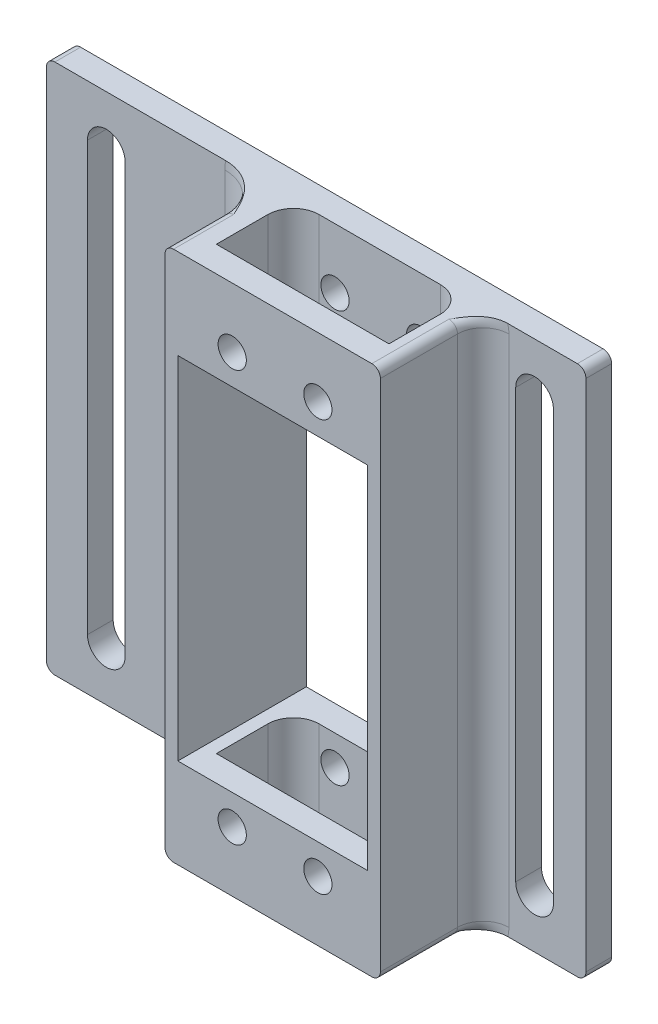
SolidWorks part; units mm, degrees
ref_plane "前视基准面" through (0, 0, 0) normal (0, 0, 1) x (1, 0, 0)
ref_plane "上视基准面" through (0, 0, 0) normal (0, 1, 0) x (1, 0, 0)
ref_plane "右视基准面" through (0, 0, 0) normal (1, 0, 0) x (0, 0, -1)
sketch "草图1" plane through (0, 0, 0) normal (0, 0, 1) x (1, 0, 0)
  line L5 (-28, 6) -> (35, 6)
  line L6 (-28, 6) -> (-28, -56)
  line L7 (-28, -56) -> (35, -56)
  line L8 (35, 6) -> (35, -56)
  line L10 (26.8, 0) -> (26.8, -50)
  line L11 (31.2, 0) -> (31.2, -50)
  line L13 (-23.2, 0) -> (-23.2, -50)
  line L14 (-18.8, 0) -> (-18.8, -50)
  arc A1 (31.2, 0) -> (26.8, 0) centre (29, 0) ccw
  arc A2 (26.8, -50) -> (31.2, -50) centre (29, -50) ccw
  arc A4 (-18.8, 0) -> (-23.2, 0) centre (-21, 0) ccw
  arc A5 (-23.2, -50) -> (-18.8, -50) centre (-21, -50) ccw
  dimension "D3" = 6
  dimension "D4" = 6
  dimension "D5" = 6
  dimension "D6" = 2
  dimension "D7" = 50
  dimension "D8" = 63
  dimension "D2" = 50
  dimension "D10" = 4.4
extrude "凸台-拉伸1" add sketch "草图1" along normal blind 3
sketch "草图2" plane through (0, 0, 3) normal (0, 0, 1) x (1, 0, 0)
  line L0 (35, 6) -> (-28, 6) construction
  line L6 (-2.15, 6) -> (23, 6)
  line L7 (-2.15, 6) -> (-2.15, -56)
  line L8 (-2.15, -56) -> (23, -56)
  line L9 (23, 6) -> (23, -56)
  line L13 (35, -56) -> (35, 6) construction
  circle A0 centre (5.7, -1) radius 1.65
  circle A1 centre (15.7, -1) radius 1.65
  circle A2 centre (15.7, -49) radius 1.65
  circle A3 centre (5.7, -49) radius 1.65
  dimension "D4" = 7
  dimension "D5" = 62
  dimension "D6" = 25.15
  dimension "D7" = 7
  dimension "D3" = 7.85
  dimension "D1" = 10
  dimension "D2" = 48
  dimension "D8" = 62
  dimension "D9" = 12
extrude "凸台-拉伸2" add sketch "草图2" along normal blind 12
sketch "草图4" plane through (0, 0, 15) normal (0, 0, 1) x (1, 0, 0)
  line L1 (-0.65, -4.5) -> (21.5, -4.5)
  line L2 (-0.65, -4.5) -> (-0.65, -45.5)
  line L3 (-0.65, -45.5) -> (21.5, -45.5)
  line L4 (21.5, -4.5) -> (21.5, -45.5)
  line L5 (-2.15, 6) -> (-2.15, -56) construction
  line L6 (23, -56) -> (23, 6) construction
  line L7 (23, 6) -> (-2.15, 6) construction
  line L8 (-2.15, -56) -> (23, -56) construction
  circle A0 centre (5.7, -1) radius 1.65
  circle A1 centre (5.7, -49) radius 1.65
  circle A2 centre (15.7, -49) radius 1.65
  circle A3 centre (15.7, -1) radius 1.65
  dimension "D1" = 1.5
  dimension "D2" = 1.5
  dimension "D3" = 10.5
  dimension "D4" = 10.5
extrude "切除-拉伸4" cut sketch "草图4" against normal blind 45
fillet "圆角1" radius 1 8 edges at (-28, -56, 1.5) (35, -56, 1.5) (35, 6, 1.5) (-28, 6, 1.5) (-2.15, 6, 9) (23, 6, 9) (23, -56, 9) (-2.15, -56, 9)
fillet "圆角2" radius 5 3 edges at (-1.8571, 5.7071, 3) (-1.8571, -55.7071, 3) (-2.15, -25, 3)
sketch "草图5" plane through (0, -56, 0) normal (0, -1, 0) x (-1, 0, 0)
  line L1 (-0.85, -12) -> (-21, -12)
  line L2 (-0.85, -12) -> (-0.85, -3)
  line L3 (-0.85, -3) -> (-21, -3)
  line L4 (-21, -12) -> (-21, -3)
  line L5 (-23, -15) -> (-23, -3) construction
  line L6 (1.15, -15) -> (-22, -15) construction
  dimension "D2" = 2
  dimension "D3" = 3
  dimension "D4" = 3
extrude "切除-拉伸5" cut sketch "草图5" against normal blind 70
fillet "圆角3" radius 3 4 edges at (0.85, 0.75, 3) (21, 0.75, 3) (21, -50.75, 3) (0.85, -50.75, 3)
fillet "圆角4" radius 3 3 edges at (22.7071, -55.7071, 3) (22.7071, 5.7071, 3) (23, -25, 3)
